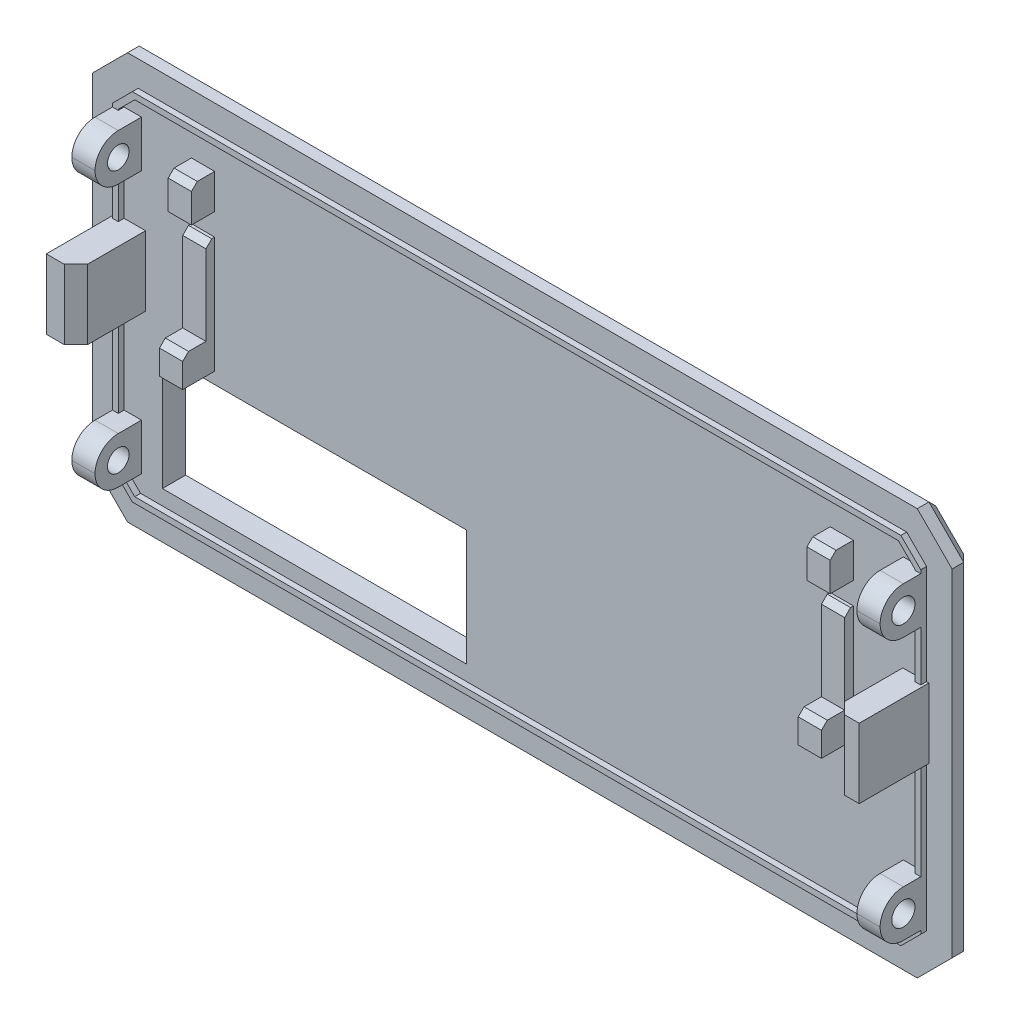
SolidWorks part; units mm, degrees
ref_plane "前视基准面" through (0, 0, 0) normal (0, 0, 1) x (1, 0, 0)
ref_plane "上视基准面" through (0, 0, 0) normal (0, 1, 0) x (1, 0, 0)
ref_plane "右视基准面" through (0, 0, 0) normal (1, 0, 0) x (0, 0, -1)
other "Configuration Table"
sketch "草图1" plane through (0, 0, 0) normal (0, 0, 1) x (1, 0, 0)
  line L0 (-39.7638, 14.7992) -> (-36.7638, 17.7992)
  line L5 (-36.7638, 17.7992) -> (31.2362, 17.7992)
  line L6 (-39.7638, 14.7992) -> (-39.7638, -14.2008)
  line L7 (-36.7638, -17.2008) -> (31.2362, -17.2008)
  line L8 (34.2362, 14.7992) -> (34.2362, -14.2008)
  line L9 (-39.7638, -14.2008) -> (-36.7638, -17.2008)
  line L10 (31.2362, -17.2008) -> (34.2362, -14.2008)
  line L11 (31.2362, 17.7992) -> (34.2362, 14.7992)
  point P0 (-39.7638, 17.7992)
  point P1 (34.2362, -17.2008)
  point P2 (-39.7638, -17.2008)
  point P3 (34.2362, 17.7992)
  dimension "D1" = 74
  dimension "D2" = 35
extrude "凸台-拉伸1" add sketch "草图1" along normal blind 2
chamfer "倒角1" distance 1 angle 45 8 edges at (-38.2638, 16.2992, 0) (-2.7638, -17.2008, 0) (-39.7638, 0.2992, 0) (-38.2638, -15.7008, 0) (32.7362, -15.7008, 0) (34.2362, 0.2992, 0) (32.7362, 16.2992, 0) (-2.7638, 17.7992, 0)
sketch "草图3" plane through (0, 0, 2) normal (0, 0, 1) x (1, 0, 0)
  line L0 (-36.7638, 17.7992) -> (31.2362, 17.7992) construction
  line L1 (-37.5638, 13.5992) -> (-35.5638, 13.5992)
  line L2 (-37.5638, 13.5992) -> (-37.5638, 9.5992)
  line L3 (-37.5638, 9.5992) -> (-35.5638, 9.5992)
  line L4 (-35.5638, 13.5992) -> (-35.5638, 9.5992)
  line L5 (-37.5638, -13.0008) -> (-35.5638, -13.0008)
  line L6 (-37.5638, -13.0008) -> (-37.5638, -9.0008)
  line L7 (-37.5638, -9.0008) -> (-35.5638, -9.0008)
  line L8 (-35.5638, -13.0008) -> (-35.5638, -9.0008)
  line L9 (32.0362, 13.5992) -> (30.0362, 13.5992)
  line L10 (32.0362, 13.5992) -> (32.0362, 9.5992)
  line L11 (32.0362, 9.5992) -> (30.0362, 9.5992)
  line L12 (30.0362, 13.5992) -> (30.0362, 9.5992)
  line L13 (32.0362, -13.0008) -> (30.0362, -13.0008)
  line L14 (32.0362, -13.0008) -> (32.0362, -9.0008)
  line L15 (32.0362, -9.0008) -> (30.0362, -9.0008)
  line L16 (30.0362, -13.0008) -> (30.0362, -9.0008)
  line L17 (-39.7638, -14.2008) -> (-39.7638, 14.7992) construction
  line L18 (34.2362, 14.7992) -> (34.2362, -14.2008) construction
  line L19 (31.2362, -17.2008) -> (-36.7638, -17.2008) construction
  dimension "D1" = 2
  dimension "D2" = 4
  dimension "D3" = 4.2
  dimension "D4" = 2.2
  dimension "D5" = 2.2
  dimension "D6" = 4.2
extrude "凸台-拉伸2" add sketch "草图3" along normal blind 4
fillet "圆角1" radius 2 8 edges at (31.0362, 13.5992, 6) (31.0362, 9.5992, 6) (31.0362, -9.0008, 6) (31.0362, -13.0008, 6) (-36.5638, -13.0008, 6) (-36.5638, -9.0008, 6) (-36.5638, 13.5992, 6) (-36.5638, 9.5992, 6)
sketch "草图4" plane through (32.0362, 0, 0) normal (1, 0, 0) x (0, 0, -1)
  circle A0 centre (-4, 11.5992) radius 1
  circle A1 centre (-4, -11.0008) radius 1
  dimension "D1" = 2
extrude "切除-拉伸1" cut sketch "草图4" against normal up to next (2 mm away) draft 2
sketch "草图5" plane through (-37.5638, 0, 0) normal (-1, 0, 0) x (0, 0, 1)
  circle A0 centre (4, 11.5992) radius 1
  circle A1 centre (4, -11.0008) radius 1
  dimension "D1" = 2
extrude "切除-拉伸2" cut sketch "草图5" against normal up to next (2 mm away) draft 2
sketch "草图6" plane through (0, 0, 2) normal (0, 0, 1) x (1, 0, 0)
  line L0 (31.2362, 17.7992) -> (-36.7638, 17.7992) construction
  line L1 (-31.2638, 7.7992) -> (-29.2638, 7.7992)
  line L2 (-31.2638, 7.7992) -> (-31.2638, -2.2008)
  line L3 (-31.2638, -2.2008) -> (-29.2638, -2.2008)
  line L4 (-29.2638, 7.7992) -> (-29.2638, -2.2008)
  line L5 (23.7362, 7.7992) -> (25.7362, 7.7992)
  line L6 (23.7362, 7.7992) -> (23.7362, -2.2008)
  line L7 (23.7362, -2.2008) -> (25.7362, -2.2008)
  line L8 (25.7362, 7.7992) -> (25.7362, -2.2008)
  line L9 (-39.7638, 14.7992) -> (-39.7638, -14.2008) construction
  line L10 (34.2362, -14.2008) -> (34.2362, 14.7992) construction
  dimension "D1" = 10
  dimension "D2" = 10
  dimension "D3" = 8.5
  dimension "D4" = 8.5
  dimension "D5" = 10
  dimension "D6" = 2
extrude "凸台-拉伸3" add sketch "草图6" along normal blind 0.75
sketch "草图7" plane through (0, 0, 2.75) normal (0, 0, 1) x (1, 0, 0)
  line L0 (-29.2638, -2.2008) -> (-29.2638, 7.7992) construction
  line L1 (-31.2638, -2.2008) -> (-29.2638, -2.2008)
  line L2 (-31.2638, -2.2008) -> (-31.2638, 0.3992)
  line L3 (-31.2638, 0.3992) -> (-29.2638, 0.3992)
  line L4 (-29.2638, -2.2008) -> (-29.2638, 0.3992)
  line L5 (25.7362, -2.2008) -> (25.7362, 7.7992) construction
  line L6 (23.7362, -2.2008) -> (25.7362, -2.2008)
  line L7 (23.7362, -2.2008) -> (23.7362, 0.3992)
  line L8 (23.7362, 0.3992) -> (25.7362, 0.3992)
  line L9 (25.7362, -2.2008) -> (25.7362, 0.3992)
  dimension "D1" = 2.6
extrude "凸台-拉伸4" add sketch "草图7" along normal blind 2
chamfer "倒角2" distance 0.5 angle 45 4 edges at (24.7362, 7.7992, 2.75) (24.7362, 0.3992, 4.75) (-30.2638, 7.7992, 2.75) (-30.2638, 0.3992, 4.75)
sketch "草图8" plane through (0, 0, 2) normal (0, 0, 1) x (1, 0, 0)
  line L0 (-37.7638, 13.9708) -> (-37.7638, -13.3724) construction
  line L1 (-37.7638, 5.2992) -> (-35.2138, 5.2992)
  line L2 (-37.7638, 5.2992) -> (-37.7638, -0.7008)
  line L3 (-37.7638, -0.7008) -> (-35.2138, -0.7008)
  line L4 (-35.2138, 5.2992) -> (-35.2138, -0.7008)
  line L5 (31.2362, 17.7992) -> (-36.7638, 17.7992) construction
  line L6 (32.2362, -13.3724) -> (32.2362, 13.9708) construction
  line L7 (32.2362, 5.2992) -> (29.9862, 5.2992)
  line L8 (32.2362, 5.2992) -> (32.2362, -0.7008)
  line L9 (32.2362, -0.7008) -> (29.9862, -0.7008)
  line L10 (29.9862, 5.2992) -> (29.9862, -0.7008)
  dimension "D1" = 12.5
  dimension "D2" = 6
  dimension "D3" = 2.55
  dimension "D4" = 2.25
extrude "凸台-拉伸5" add sketch "草图8" along normal blind 6
chamfer "倒角3" distance 1 angle 45 2 edges at (29.9862, 2.2992, 8) (-35.2138, 2.2992, 8)
sketch "草图9" plane through (0, 0, 2) normal (0, 0, 1) x (1, 0, 0)
  line L0 (31.2362, 17.7992) -> (-36.7638, 17.7992) construction
  line L1 (-31.2638, 12.6992) -> (-29.2638, 12.6992)
  line L2 (-31.2638, 12.6992) -> (-31.2638, 9.6992)
  line L3 (-31.2638, 9.6992) -> (-29.2638, 9.6992)
  line L4 (-29.2638, 12.6992) -> (-29.2638, 9.6992)
  line L5 (23.7362, 12.6992) -> (25.7362, 12.6992)
  line L6 (23.7362, 12.6992) -> (23.7362, 9.6992)
  line L7 (23.7362, 9.6992) -> (25.7362, 9.6992)
  line L8 (25.7362, 12.6992) -> (25.7362, 9.6992)
  line L9 (34.2362, -14.2008) -> (34.2362, 14.7992) construction
  line L10 (-39.7638, 14.7992) -> (-39.7638, -14.2008) construction
  dimension "D1" = 5.1
  dimension "D2" = 8.5
  dimension "D3" = 2
  dimension "D4" = 3
  dimension "D5" = 8.5
extrude "凸台-拉伸6" add sketch "草图9" along normal blind 2
chamfer "倒角4" distance 0.5 angle 45 2 edges at (24.7362, 12.6992, 4) (-30.2638, 12.6992, 4)
sketch "草图10" plane through (0, 0, 0) normal (0, 0, -1) x (-1, 0, 0)
  line L0 (36.7638, -17.2008) -> (-31.2362, -17.2008) construction
  line L1 (7.5638, -3.2008) -> (33.7638, -3.2008)
  line L2 (7.5638, -3.2008) -> (7.5638, -13.2008)
  line L3 (7.5638, -13.2008) -> (33.7638, -13.2008)
  line L4 (33.7638, -3.2008) -> (33.7638, -13.2008)
  line L5 (39.7638, 14.7992) -> (39.7638, -14.2008) construction
  dimension "D1" = 4
  dimension "D2" = 10
  dimension "D3" = 6
  dimension "D4" = 26.2
extrude "切除-拉伸3" cut sketch "草图10" against normal up to next
sketch "草图11" plane through (0, 0, 2) normal (0, 0, 1) x (1, 0, 0)
  line L8 (30.1178, 15.0992) -> (-35.6455, 15.0992)
  line L9 (-35.6455, 15.0992) -> (-37.0638, 13.6808)
  line L10 (-37.0638, 13.6808) -> (-37.0638, -13.0824)
  line L11 (-37.0638, -13.0824) -> (-35.6455, -14.5008)
  line L12 (-35.6455, -14.5008) -> (30.1178, -14.5008)
  line L13 (30.1178, -14.5008) -> (31.5362, -13.0824)
  line L14 (31.5362, -13.0824) -> (31.5362, 13.6808)
  line L15 (31.5362, 13.6808) -> (30.1178, 15.0992)
  line L16 (30.3249, 15.5992) -> (-35.8526, 15.5992)
  line L17 (-35.8526, 15.5992) -> (-37.5638, 13.8879)
  line L18 (-37.5638, 13.8879) -> (-37.5638, -13.2895)
  line L19 (-37.5638, -13.2895) -> (-35.8526, -15.0008)
  line L20 (-35.8526, -15.0008) -> (30.3249, -15.0008)
  line L21 (30.3249, -15.0008) -> (32.0362, -13.2895)
  line L22 (32.0362, -13.2895) -> (32.0362, 13.8879)
  line L23 (32.0362, 13.8879) -> (30.3249, 15.5992)
  line L24 (30.3249, 15.5992) -> (-35.8526, 15.5992)
  line L25 (-35.8526, 15.5992) -> (-37.5638, 13.8879)
  line L26 (-37.5638, 13.8879) -> (-37.5638, -13.2895)
  line L27 (-37.5638, -13.2895) -> (-35.8526, -15.0008)
  line L28 (-35.8526, -15.0008) -> (30.3249, -15.0008)
  line L29 (30.3249, -15.0008) -> (32.0362, -13.2895)
  line L30 (32.0362, -13.2895) -> (32.0362, 13.8879)
  line L31 (32.0362, 13.8879) -> (30.3249, 15.5992)
  dimension "D1" = 2.2
  dimension "D2" = 0.5
extrude "凸台-拉伸7" add sketch "草图11" along normal blind 0.5
